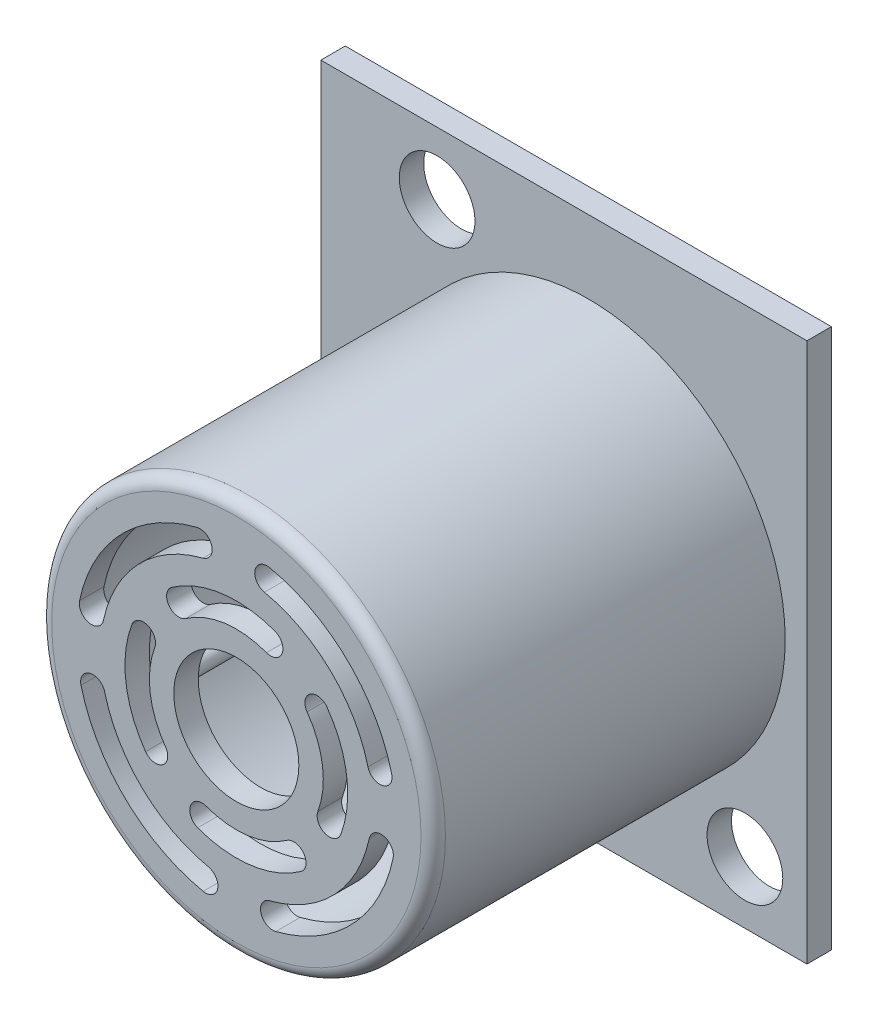
SolidWorks part; units mm, degrees
ref_plane "Front Plane" through (0, 0, 0) normal (0, 0, 1) x (1, 0, 0)
ref_plane "Top Plane" through (0, 0, 0) normal (0, 1, 0) x (1, 0, 0)
ref_plane "Right Plane" through (0, 0, 0) normal (1, 0, 0) x (0, 0, -1)
sketch "Sketch1" plane through (0, 0, 0) normal (0, 0, 1) x (1, 0, 0)
  line L1 (0, 0) -> (19.9, 0)
  line L2 (0, 0) -> (0, -22.1)
  line L3 (0, -22.1) -> (19.9, -22.1)
  line L4 (19.9, 0) -> (19.9, -22.1)
  dimension "D1" = 19.9
  dimension "D2" = 22.1
extrude "Extrude1" add sketch "Sketch1" along normal blind 1
sketch "Sketch2" plane through (0, 0, 1) normal (0, 0, 1) x (1, 0, 0)
  line L0 (19.9, 0) -> (0, 0) construction
  line L1 (0, -22.1) -> (19.9, -22.1) construction
  line L2 (19.9, -22.1) -> (19.9, 0) construction
  circle A0 centre (4.76, -2.56) radius 1.55
  circle A1 centre (17.36, -19.56) radius 1.55
  dimension "D3" = 3.1
  dimension "D4" = 3.1
  dimension "D1" = 2.56
  dimension "D2" = 2.54
  dimension "D5" = 2.54
  dimension "D6" = 12.6
extrude "Extrude2" cut sketch "Sketch2" against normal blind 1
sketch "Sketch3" plane through (0, 0, 1) normal (0, 0, 1) x (1, 0, 0)
  line L0 (19.9, -22.1) -> (19.9, 0) construction
  line L1 (19.9, 0) -> (0, 0) construction
  circle A0 centre (10.95, -11.05) radius 8.06
  dimension "D1" = 16.12
  dimension "D2" = 8.95
  dimension "D3" = 11.05
extrude "Extrude3" add sketch "Sketch3" along normal blind 14.41
fillet "Fillet1" radius 0.5 1 edges at (19.01, -11.05, 15.41)
sketch "Sketch4" plane through (0, 0, 15.41) normal (0, 0, 1) x (1, 0, 0)
  circle A0 centre (10.95, -11.05) radius 7.56
  arc A1 (4.4436, -14.8997) -> (4.0858, -14.218) centre (4.256, -14.5634) ccw
extrude "Extrude4" cut sketch "Sketch4" against normal blind 14 contours A1 A0 region at (10.9584, -11.0456, 15.41)
sketch "Sketch5" plane through (0, 0, 1.41) normal (0, 0, 1) x (1, 0, 0)
  circle A0 centre (10.95, -11.05) radius 4.0802
extrude "Extrude5" add sketch "Sketch5" along normal blind 6
sketch "Sketch6" plane through (0, 0, 15.41) normal (0, 0, 1) x (1, 0, 0)
  circle A0 centre (10.95, -11.05) radius 7.56
extrude "Extrude6" add sketch "Sketch6" against normal blind 1
sketch "Sketch7" plane through (0, 0, 15.41) normal (0, 0, 1) x (1, 0, 0)
  line L0 (10.95, -11.05) -> (4.5319, -9.6929) construction
  line L1 (4.5319, -9.6929) -> (10.95, -11.05) construction
  line L2 (10.95, -11.05) -> (9.336, -4.6916) construction
  line L3 (10.95, -11.05) -> (8.5143, -4.9589) construction
  line L4 (8.5143, -4.9589) -> (10.95, -11.05) construction
  line L5 (10.95, -11.05) -> (4.7968, -8.7759) construction
  line L6 (10.95, -11.05) -> (10.95, -8.49) construction
  line L7 (10.95, -8.49) -> (10.95, -11.05) construction
  line L8 (10.95, -11.05) -> (8.39, -11.05) construction
  line L9 (10.95, -11.05) -> (7.2349, -13.6942) construction
  arc A0 (4.5319, -9.6929) -> (9.336, -4.6916) centre (10.95, -11.05) cw
  circle A1 centre (10.95, -11.05) radius 5.56
  circle A2 centre (10.95, -11.05) radius 6.56
  circle A3 centre (10.95, -11.05) radius 6.56
  circle A4 centre (10.95, -11.05) radius 4.56
  circle A5 centre (10.95, -11.05) radius 3.56
  circle A6 centre (10.95, -11.05) radius 2.56
  arc A7 (9.5821, -5.6609) -> (5.5103, -9.8998) centre (10.95, -11.05) ccw
  arc A8 (4.5319, -9.6929) -> (5.5103, -9.8998) centre (5.0211, -9.7964) ccw
  arc A9 (9.336, -4.6916) -> (9.5821, -5.6609) centre (9.459, -5.1763) cw
  arc A10 (6.6728, -9.4692) -> (7.2349, -13.6942) centre (10.95, -11.05) ccw
  arc A11 (7.6108, -9.8159) -> (8.0537, -13.12) centre (10.95, -11.05) ccw
  arc A12 (7.2349, -13.6942) -> (8.0537, -13.12) centre (7.6423, -13.4042) ccw
  arc A13 (6.6728, -9.4692) -> (7.6108, -9.8159) centre (7.1418, -9.6425) cw
  dimension "D1" = 1
  dimension "D2" = 1
  dimension "D3" = 1
  dimension "D4" = 1
  dimension "D5" = 1
extrude "Extrude7" cut sketch "Sketch7" against normal blind 1 contours A9 A0 A8 A1 | A13 A4 A12 A5 | A6 region at (6.8477, -7.1095, 15.41) region at (7.1336, -11.5578, 15.41) region at (10.95, -11.05, 15.41)
pattern_circular "CirPattern1" count 4 over 360 about axis through (10.95, -11.05, 15.41) along (0, 0, -1) of "Extrude7"
